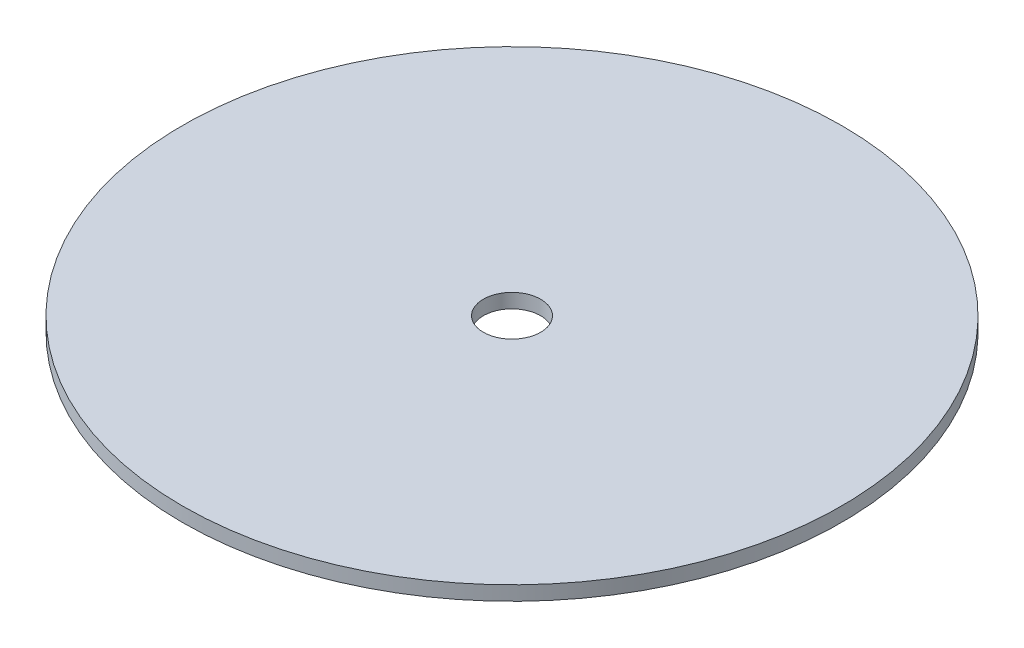
SolidWorks part; units mm, degrees
ref_plane "Front Plane" through (0, 0, 0) normal (0, 0, 1) x (1, 0, 0)
ref_plane "Top Plane" through (0, 0, 0) normal (0, 1, 0) x (1, 0, 0)
ref_plane "Right Plane" through (0, 0, 0) normal (1, 0, 0) x (0, 0, -1)
sketch "Sketch1" plane through (0, 0, 0) normal (0, 1, 0) x (1, 0, 0)
  circle A0 centre (0, 0) radius 73.0293
extrude "Boss-Extrude1" add sketch "Sketch1" along normal blind 3.175 contours A0
sketch "Sketch8" plane through (0, 3.175, 0) normal (0, 1, 0) x (1, 0, 0)
  circle A0 centre (0, 0) radius 6.35
extrude "Cut-Extrude3" cut sketch "Sketch8" against normal blind 16.256
